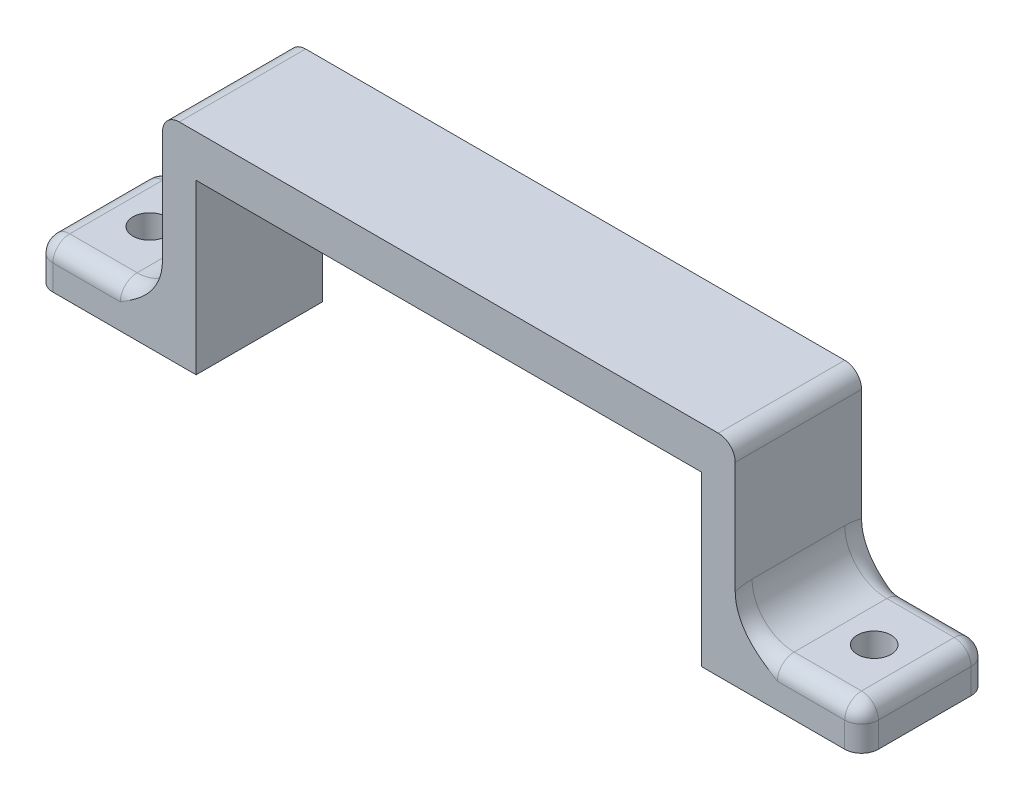
SolidWorks part; units mm, degrees
ref_plane "Front Plane" through (0, 0, 0) normal (0, 0, 1) x (1, 0, 0)
ref_plane "Top Plane" through (0, 0, 0) normal (0, 1, 0) x (1, 0, 0)
ref_plane "Right Plane" through (0, 0, 0) normal (1, 0, 0) x (0, 0, -1)
sketch "Sketch1" plane through (0, 0, 0) normal (0, 1, 0) x (1, 0, 0)
  line L1 (0, 0) -> (-60, 0)
  line L2 (0, 0) -> (0, -15)
  line L3 (0, -15) -> (-60, -15)
  line L4 (-60, 0) -> (-60, -15)
  line L5 (0, 0) -> (4, 0)
  line L6 (0, 0) -> (0, -15)
  line L7 (0, -15) -> (4, -15)
  line L8 (4, 0) -> (4, -15)
  line L9 (-60, 0) -> (-64, 0)
  line L10 (-60, 0) -> (-60, -15)
  line L11 (-60, -15) -> (-64, -15)
  line L12 (-64, 0) -> (-64, -15)
  line L13 (4, 0) -> (19, 0)
  line L14 (4, 0) -> (4, -15)
  line L15 (4, -15) -> (19, -15)
  line L16 (19, 0) -> (19, -15)
  line L17 (-64, 0) -> (-79, 0)
  line L18 (-64, 0) -> (-64, -15)
  line L19 (-64, -15) -> (-79, -15)
  line L20 (-79, 0) -> (-79, -15)
  dimension "D1" = 60
  dimension "D2" = 15
  dimension "D3" = 4
  dimension "D4" = 15
extrude "Boss-Extrude1" add sketch "Sketch1" along normal blind 25 contours L17 L20 L19 L12 | L9 L12 L11 L4 | L1 L4 L3 L2 | L8 L5 L2 L7 | L16 L13 L8 L15 region at (-30, 0, 7.5) region at (2, 0, 7.5) region at (-62, 0, 7.5) region at (11.5, 0, 7.5) region at (-71.5, 0, 7.5)
extrude "Cut-Extrude1" cut sketch "Sketch1<3>" along normal blind 20 contours L1 L4 L3 L2 region at (-30, 0, 7.5)
sketch "Sketch1<3>" plane through (0, 0, 0) normal (0, 1, 0) x (1, 0, 0) same geometry as "Sketch1"
extrude "Cut-Extrude2" cut sketch "Sketch1<4>" against normal offset from surface (20 mm away) 5 from surface contours L17 L20 L19 L12 | L16 L13 L8 L15 region at (11.5, 0, 7.5) region at (-71.5, 0, 7.5) up to face at (9.5, 0, 7.5) starting at face at (-30, 25, 7.5)
sketch "Sketch1<4>" plane through (0, 0, 0) normal (0, 1, 0) x (1, 0, 0) same geometry as "Sketch1"
fillet "Fillet1" radius 2 6 edges at (19, 2.5, 0) (19, 2.5, 15) (-79, 2.5, 0) (-79, 2.5, 15) (4, 25, 7.5) (-64, 25, 7.5)
fillet "Fillet2" radius 2 10 edges at (-70.5, 5, 15) (-78.4142, 5, 14.4142) (-79, 5, 7.5) (-78.4142, 5, 0.5858) (10.5, 5, 15) (18.4142, 5, 14.4142) (19, 5, 7.5) (18.4142, 5, 0.5858) (-70.5, 5, 0) (10.5, 5, 0)
fillet "Fillet3" radius 5 6 edges at (-64, 4.4142, 0.5858) (-64, 4.4142, 14.4142) (4, 4.4142, 0.5858) (4, 4.4142, 14.4142) (-64, 5, 7.5) (4, 5, 7.5)
sketch "Sketch2" plane through (0, 5, 0) normal (0, 1, 0) x (1, 0, 0)
  line L0 (9, -13) -> (17, -13) construction
  line L2 (17, -13) -> (17, -2) construction
  line L3 (-77, -2) -> (-77, -13) construction
  circle A0 centre (13, -7.5) radius 2
  circle A1 centre (-73, -7.5) radius 2
  point P4 (0, 0)
  point P5 (0, 0)
  dimension "D1" = 4
  dimension "D2" = 5.5
  dimension "D3" = 4
  dimension "D4" = 4
extrude "Cut-Extrude3" cut sketch "Sketch2" against normal up to next
